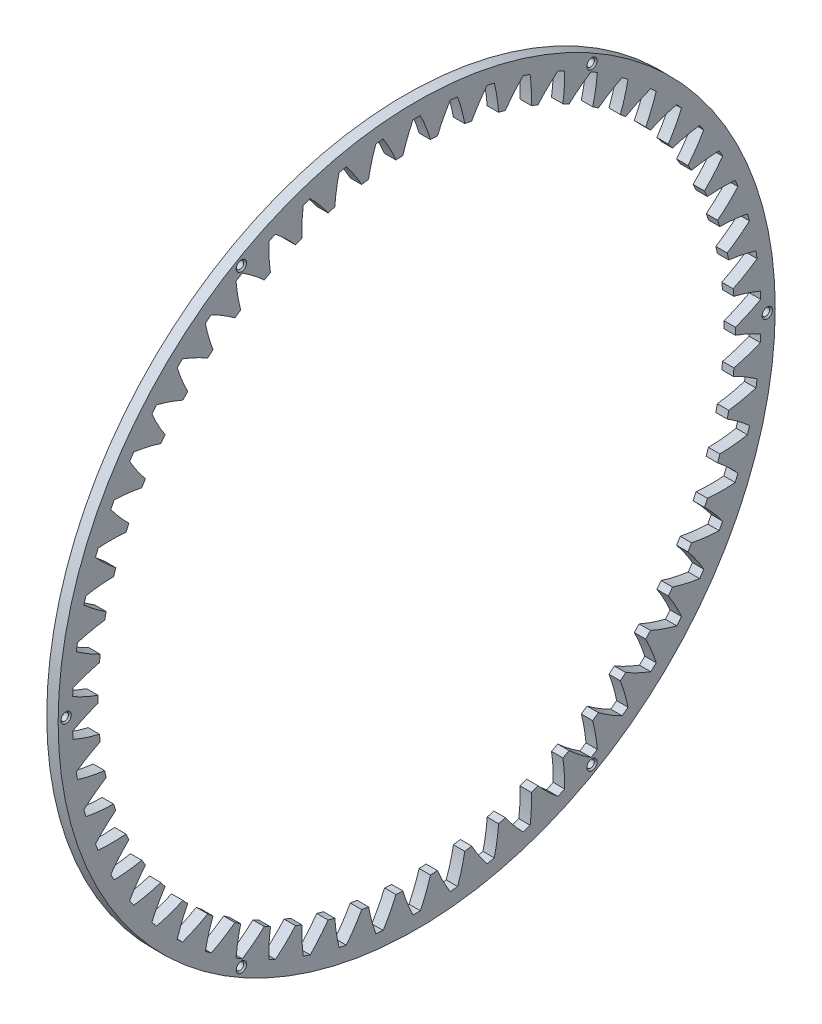
SolidWorks part; units mm, degrees
ref_plane "Plane1" through (0, 0, 0) normal (0, 0, 1) x (1, 0, 0)
ref_plane "Plane2" through (0, 0, 0) normal (0, 1, 0) x (1, 0, 0)
ref_plane "Plane3" through (0, 0, 0) normal (1, 0, 0) x (0, 0, -1)
other "Configuration Table"
sketch "HoldingSke" plane through (0, 0, 0) normal (0, 1, 0) x (1, 0, 0)
  line L0 (0, 0) -> (0.106, -0.1696)
  line L1 (-15, 0) -> (100, 0) construction
  line L2 (0, 0) -> (-2.1039, 2.3779)
  line L3 (0, 0) -> (-11.863, 4.5341)
  line L4 (0, 0) -> (4.5764, 7.3237)
  line L5 (0, 0) -> (-23.7986, -8.8762)
  line L6 (0, 0) -> (-10.5278, -7.1032)
  line L7 (-2.1039, 2.3779) -> (3.3635, 27.1825)
  line L8 (-76.2, 7.3779) -> (-54.61, 7.3779)
  line L9 (-71.009, 38.7566) -> (-53.1078, 45.2721)
  line L10 (-76.2, 71.12) -> (104.1128, 71.12)
  line L11 (0, 0) -> (-5, 0)
  line L12 (-76.2, 101.6) -> (-76.033, 101.6)
  line L13 (24.9733, 27.94) -> (52.9518, 28.4284)
  line L14 (24.9733, 27.94) -> (24.9743, 27.94)
  line L15 (24.9733, 27.94) -> (100.4006, 29.5858)
  circle A0 centre (0, 0) radius 157.5
  circle A1 centre (0, 0) radius 12.7
  circle A2 centre (0, 0) radius 12.7
  dimension "Num_teeth" = 58
  dimension "Pitch_radius" = 180.3128
  dimension "Width" = 5
  dimension "Diameter" = 315
sketch "BasProSke" plane through (0, 0, 0) normal (0, 1, 0) x (1, 0, 0)
  line L0 (-10, 0) -> (60, 0) construction
  line L1 (0, 140) -> (0, 157.5)
  line L2 (0, 140) -> (5, 140)
  line L3 (5, 140) -> (5, 157.5)
  line L4 (5, 157.5) -> (0, 157.5)
  dimension "Thickness" = 5
  dimension "Diameter" = 315
revolve "Base-Revolve" add sketch "BasProSke" angle 360 about L0
sketch "TooCutSke" plane through (0, 0, 0) normal (1, 0, 0) x (0, 0, -1)
  line L3 (4.344, 144.9349) -> (4.344, 53.6633) construction
  line L4 (0, 0) -> (0, 59.563) construction
  line L5 (0, 0) -> (-3.6992, 68.2273) construction
  line L6 (-63.498, 119.3672) -> (31.1483, 124.4988) construction
  circle A0 centre (0, 0) radius 145 construction
  circle A1 centre (0, 0) radius 151.251 construction
  circle A2 centre (0, 0) radius 122.6299 construction
  circle A3 centre (0, 0) radius 139.9746 construction
  arc A4 (6.0502, 139.8438) -> (1.619, 151.2423) centre (-63.498, 119.3672) ccw
  arc A5 (6.0502, 139.8438) -> (-6.0502, 139.8438) centre (0, 0) ccw
  arc A6 (1.619, 151.2423) -> (-1.619, 151.2423) centre (0, 0) ccw
  arc A7 (-1.619, 151.2423) -> (-6.0502, 139.8438) centre (63.498, 119.3672) ccw
extrude "ToothCut" cut sketch "TooCutSke" along normal through all
fillet "Breaks" [suppressed] radius 0.5
fillet "RootFillets" [suppressed] radius 1.251
pattern_circular "TeethCuts" count 58 every 6.207 about axis through (-10, 0, 0) along (1, 0, 0) of "RootFillets", "Breaks", "ToothCut"
sketch "Sketch3" plane through (5, 0, 0) normal (1, 0, 0) x (0, 0, -1)
  line L0 (-154, 0) -> (-77, 133.3679)
  line L1 (-77, 133.3679) -> (77, 133.3679)
  line L2 (77, 133.3679) -> (154, 0)
  line L3 (154, 0) -> (77, -133.3679)
  line L4 (77, -133.3679) -> (-77, -133.3679)
  line L7 (-154, 0) -> (-77, -133.3679)
  circle A0 centre (0, 0) radius 154
  point P0 (-154, 0)
  point P2 (154, 0)
  point P4 (77, 133.3679)
  point P6 (-77, 133.3679)
  point P8 (-77, -133.3679)
  point P10 (77, -133.3679)
  dimension "D1" = 308
hole_wizard "M4x0.7 Tapped Hole1" positions "Sketch3" profile "Sketch2" tap size "M4x0.7" standard "ANSI Metric" end condition through all
sketch "Sketch2" plane through (5, 0, 154) normal (0, 1, 0) x (0, 0, -1)
  line L0 (0, 0) -> (0, 5)
  line L1 (0, 5) -> (1.65, 5)
  line L2 (1.65, 5) -> (1.65, 0.625)
  line L3 (1.65, 0.625) -> (2.275, 0)
  line L5 (2.275, 0) -> (0, 0)
  line L6 (-1.65, 0.625) -> (-2.275, 0) construction
  line L11 (0, -6.35) -> (0, 107.95) construction
  dimension "Thru Tap Drill Dia." = 3.3
  dimension "Thru Tap Drill Depth" = 5
  dimension "Near C'Sink Dia." = 4.55
  dimension "Near C'Sink Angle" = 90
cosmetic thread "Hole Thread1" parameters "D2"=4
cosmetic thread "Hole Thread2" parameters "D2"=4
cosmetic thread "Hole Thread3" parameters "D2"=4
cosmetic thread "Hole Thread4" parameters "D2"=4
cosmetic thread "Hole Thread5" parameters "D2"=4
cosmetic thread "Hole Thread6" parameters "D2"=4
cosmetic thread "Hole Thread7" parameters "D2"=4
cosmetic thread "Hole Thread8" parameters "D2"=4
cosmetic thread "Hole Thread9" parameters "D2"=4
cosmetic thread "Hole Thread10" parameters "D2"=4
cosmetic thread "Hole Thread11" parameters "D2"=4
cosmetic thread "Hole Thread12" parameters "D2"=4
equation "' \"Module@HoldingSke\" = 6.35"
equation "' \"Num_teeth@HoldingSke\" = 24"
equation "' \"Ap@HoldingSke\" =  14.5"
equation "' \"Ap@HoldingSke\" = 14.5"
equation "' \"Width@HoldingSke\" = 12"
equation "' \"Diameter@HoldingSke\" = 8 * 25.4"
equation "' \"Show_teeth@HoldingSke\" = 100"
equation "' \"Backlash@HoldingSke\" = 0.009 * 25.4"
equation "' \"Addendum_fac@HoldingSke\" = 1.0"
equation "' \"Dedendum_fac@HoldingSke\" = 1.25"
equation "' \"Dedendum_add@HoldingSke\" = 0.00005 * 25.4"
equation "' \"Clearance_fac@HoldingSke\" = 0.25"
equation "\"Pitch@HoldingSke\" = 1 / \"Module@HoldingSke\" "
equation "\"Overcut_dia@TooCutSke\" = (\"Num_teeth@HoldingSke\" - 2 * \"Addendum_fac@HoldingSke\") / \"Pitch@HoldingSke\" - 0.002 * 25.4"
equation "\"Pitch_dia@TooCutSke\" = \"Num_teeth@HoldingSke\" / \"Pitch@HoldingSke\""
equation "\"Base_dia@TooCutSke\" = \"Num_teeth@HoldingSke\" / \"Pitch@HoldingSke\" * cos((\"Ap@HoldingSke\"  * 3.14159265 / 180)) * 0.90"
equation "\"Root_dia@TooCutSke\" = \"Num_teeth@HoldingSke\"  / \"Pitch@HoldingSke\" + 2 *  \"Dedendum_fac@HoldingSke\"/ \"Pitch@HoldingSke\" + \"Dedendum_add@HoldingSke\" * 2"
equation "\"Half_ang@TooCutSke\" = 180 / \"Num_teeth@HoldingSke\""
equation "\"Half_CT@TooCutSke\" = \"Num_teeth@HoldingSke\" / \"Pitch@HoldingSke\" * sin((3.14159265 / 2 / \"Num_teeth@HoldingSke\")) / 2 + 10 * \"Backlash@HoldingSke\" / 4"
equation "\"Flank_rad@TooCutSke\" = \"Num_teeth@HoldingSke\" / \"Pitch@HoldingSke\" / 4"
equation "\"Radius@RootFillets\"= \"Clearance_fac@HoldingSke\" / \"Pitch@HoldingSke\" + \"Dedendum_add@HoldingSke\""
equation "\"Break_rad@Breaks\" = 0.02 / \"Pitch@HoldingSke\" * 5"
equation "\"Num_teeth@TeethCuts\" = int( \"Show_teeth@HoldingSke\" ) + 1"
equation "\"Num_teeth@TeethCuts\" = ((sgn( \"Num_teeth@TeethCuts\" - \"Num_teeth@HoldingSke\" )-1)*( \"Num_teeth@TeethCuts\" - \"Num_teeth@HoldingSke\" ))/-2+ \"Num_teeth@HoldingSke\""
equation "\"Num_teeth@TeethCuts\" = ((sgn( \"Num_teeth@TeethCuts\" - 2.0)+1)*( \"Num_teeth@TeethCuts\" - 2.0))/2 +2.0"
equation "\"Angle@TeethCuts\" = 360.0 / \"Num_teeth@HoldingSke\""
equation "\"Diameter@BasProSke\" = \"Num_teeth@HoldingSke\"  / \"Pitch@HoldingSke\" + 2 *  \"Dedendum_fac@HoldingSke\"/ \"Pitch@HoldingSke\" + \"Dedendum_add@HoldingSke\" * 2 + 0.002 * 25.4"
equation "\"Diameter@BasProSke\" = ((sgn( \"Diameter@BasProSke\"  - \"Diameter@HoldingSke\" )+1)*( \"Diameter@BasProSke\"  - \"Diameter@HoldingSke\" ))/2 + \"Diameter@HoldingSke\""
equation "\"Inside_diameter@BasProSke\" =  (\"Num_teeth@HoldingSke\" - 2 * \"Addendum_fac@HoldingSke\") / \"Pitch@HoldingSke\" "
equation "\"Thickness@BasProSke\"  = \"Width@HoldingSke\""
